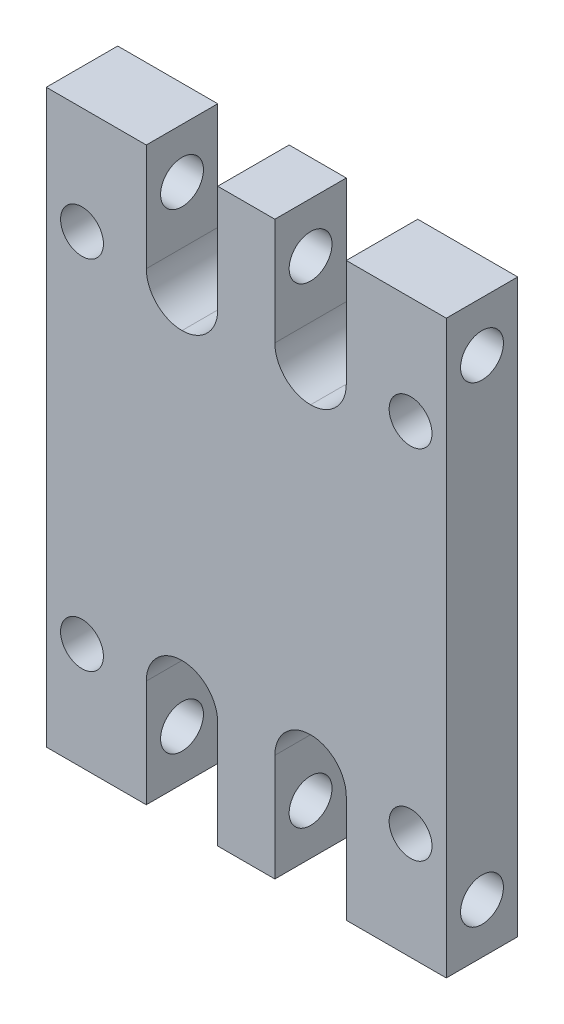
SolidWorks part; units mm, degrees
material "POM 乙缩醛共聚物"
ref_plane "前视基准面" through (0, 0, 0) normal (0, 0, 1) x (1, 0, 0)
ref_plane "上视基准面" through (0, 0, 0) normal (0, 1, 0) x (1, 0, 0)
ref_plane "右视基准面" through (0, 0, 0) normal (1, 0, 0) x (0, 0, -1)
sketch "草图1" plane through (0, 0, 0) normal (0, 0, 1) x (1, 0, 0)
  line L0 (0, 20) -> (0, -20) construction
  line L1 (-14, -20) -> (-7, -20)
  line L2 (-14, -20) -> (-14, 20)
  line L3 (-14, 20) -> (-7, 20)
  line L4 (14, -20) -> (14, 20)
  line L5 (-14, -20) -> (14, 20) construction
  line L6 (-14, 20) -> (14, -20) construction
  line L7 (-14, 0) -> (14, 0) construction
  line L9 (-7, 20) -> (-7, 10)
  line L10 (-7, 10) -> (-2, 10)
  line L11 (-2, 20) -> (-2, 10)
  line L13 (2, 20) -> (2, 10)
  line L14 (2, 10) -> (7, 10)
  line L15 (7, 20) -> (7, 10)
  line L16 (7, -20) -> (7, -10)
  line L17 (2, -10) -> (7, -10)
  line L18 (2, -20) -> (2, -10)
  line L20 (-2, -20) -> (-2, -10)
  line L21 (-7, -10) -> (-2, -10)
  line L22 (-7, -20) -> (-7, -10)
  line L24 (-2, -20) -> (2, -20)
  line L25 (7, -20) -> (14, -20)
  line L26 (7, 20) -> (14, 20)
  line L27 (-2, 20) -> (2, 20)
  circle A0 centre (-11.5, 12.5) radius 1.5
  circle A1 centre (11.5, 12.5) radius 1.5
  circle A2 centre (11.5, -12.5) radius 1.5
  circle A3 centre (-11.5, -12.5) radius 1.5
  point P0 (0, 0)
  dimension "D9" = 3
  dimension "D10" = 2.5
  dimension "D11" = 7.5
  dimension "D1" = 40
  dimension "D2" = 28
  dimension "D3" = 10
  dimension "D4" = 5
  dimension "D5" = 2
  dimension "D6" = 2
  dimension "D7" = 5
  dimension "D8" = 14
extrude "凸台-拉伸1" add sketch "草图1" along normal blind 5
fillet "圆角1" radius 2.5 8 edges at (7, -10, 2.5) (2, -10, 2.5) (-2, -10, 2.5) (-7, -10, 2.5) (7, 10, 2.5) (2, 10, 2.5) (-2, 10, 2.5) (-7, 10, 2.5)
sketch "草图3" plane through (14, 0, 0) normal (1, 0, 0) x (0, 0, -1)
  line L0 (0, 0) -> (-5, 0) construction
  line L1 (-5, -20) -> (-5, 20) construction
  line L2 (0, -20) -> (0, 20) construction
  line L3 (-5, 20) -> (0, 20) construction
  circle A0 centre (-2.5, 16.5) radius 1.5
  circle A1 centre (-2.5, -16.5) radius 1.5
  dimension "D1" = 3
  dimension "D2" = 2.5
  dimension "D3" = 3.5
extrude "切除-拉伸1" cut sketch "草图3" against normal blind 49
